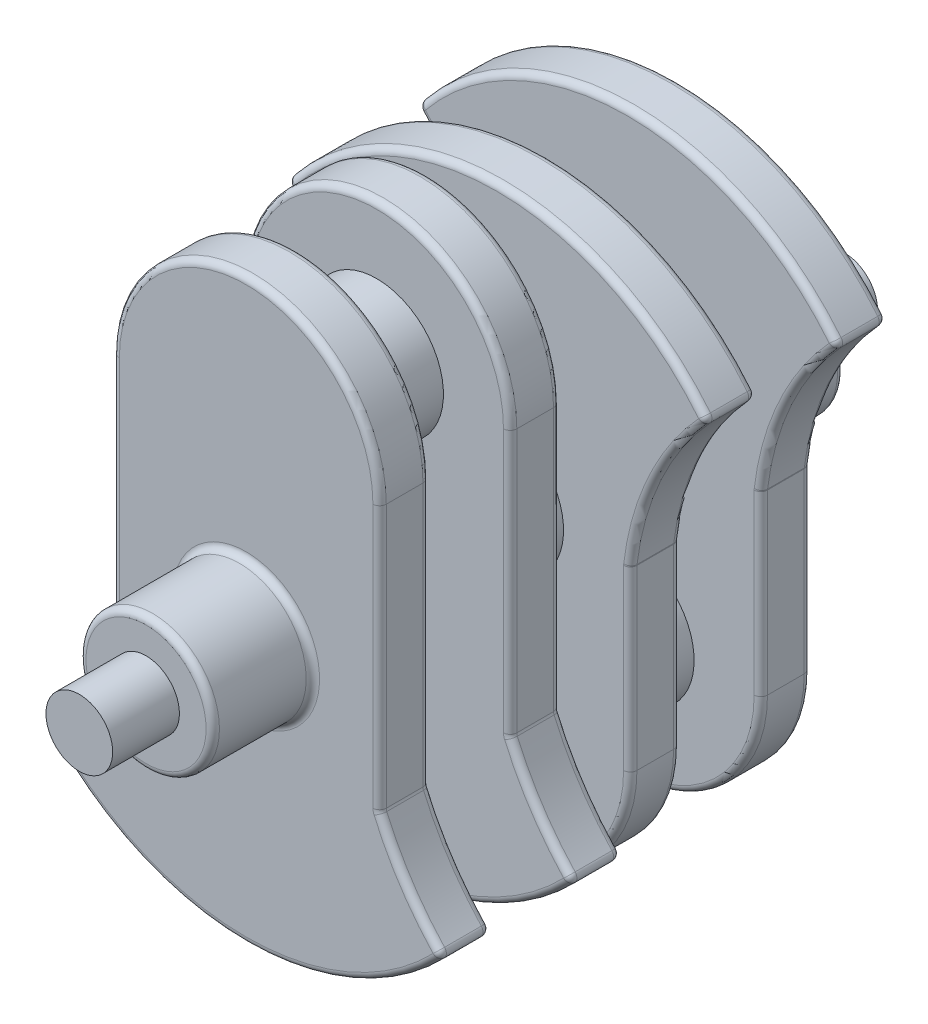
SolidWorks part; units mm, degrees
material "AISI 4340 Steel, normalized"
ref_plane "Front Plane" through (0, 0, 0) normal (0, 0, 1) x (1, 0, 0)
ref_plane "Top Plane" through (0, 0, 0) normal (0, 1, 0) x (1, 0, 0)
ref_plane "Right Plane" through (0, 0, 0) normal (1, 0, 0) x (0, 0, -1)
sketch "Sketch1" plane through (0, 0, 0) normal (0, 0, 1) x (1, 0, 0)
  circle A0 centre (0, 0) radius 20
  dimension "D1" = 20
extrude "Boss-Extrude1" add sketch "Sketch1" along normal blind 30
sketch "Sketch8" plane through (0, 0, 0) normal (0, 0, -1) x (-1, 0, 0)
  line L0 (-40, 53.333) -> (-40, -25.971)
  line L1 (40, 53.333) -> (40, -25.971)
  arc A0 (40, 53.333) -> (-40, 53.333) centre (0, 53.333) ccw
  arc A5 (-58.7669, -54.2813) -> (58.7669, -54.2813) centre (0, 0) ccw
  arc A6 (-40, -25.971) -> (-58.7669, -54.2813) centre (-125, 10) cw
  arc A7 (40, -25.971) -> (58.7669, -54.2813) centre (125, 10) ccw
  dimension "D1" = 40
  dimension "D2" = 80
  dimension "D3" = 53.333
  dimension "D5" = 10
  dimension "D6" = 125
extrude "Boss-Extrude5" add sketch "Sketch8" along normal blind 15
sketch "Sketch2" plane through (0, 0, 30) normal (0, 0, 1) x (1, 0, 0)
  circle A0 centre (0, 0) radius 10
  dimension "D1" = 10
extrude "Boss-Extrude2" add sketch "Sketch2" along normal blind 20
sketch "Sketch9" plane through (0, 0, -15) normal (0, 0, -1) x (-1, 0, 0)
  circle A0 centre (0, 53.333) radius 20
  dimension "D2" = 20
  dimension "D1" = 53.333
extrude "Boss-Extrude6" add sketch "Sketch9" along normal blind 24.13
ref_plane "Plane4" through (0, 0, -75.13) normal (0, 0, -1) x (-1, 0, 0)
sketch "Sketch10" plane through (0, 0, -39.13) normal (0, 0, -1) x (-1, 0, 0)
  line L0 (-40, -53.333) -> (-40, 0)
  line L1 (40, -53.333) -> (40, 0)
  arc A0 (-40, -53.333) -> (40, -53.333) centre (0, -53.333) ccw
  arc A1 (-40, 0) -> (-63.131, 49.1373) centre (-125, -10) ccw
  arc A2 (40, 0) -> (63.131, 49.1373) centre (125, -10) cw
  arc A3 (-63.131, 49.1373) -> (63.131, 49.1373) centre (0, 0) cw
  dimension "D1" = 40
  dimension "D5" = 10
  dimension "D3" = 80
  dimension "D2" = 53.333
  dimension "D4" = 125
extrude "Boss-Extrude7" add sketch "Sketch10" along normal blind 15 from surface starting at plane "Plane4"
ref_plane "Plane3" through (0, 0, -114.26) normal (0, 0, -1) x (-1, 0, 0)
sketch "Sketch12" plane through (0, 0, -114.26) normal (0, 0, -1) x (-1, 0, 0)
  line L2 (40, -53.333) -> (40, 0)
  line L3 (40, -53.333) -> (40, 0)
  line L4 (-40, 0) -> (-40, -53.333)
  line L5 (-40, 0) -> (-40, -53.333)
  arc A12 (-40, -53.333) -> (40, -53.333) centre (0, -53.333) ccw
  arc A13 (63.131, 49.1373) -> (40, 0) centre (125, -10) ccw
  arc A14 (63.131, 49.1373) -> (-63.131, 49.1373) centre (0, 0) ccw
  arc A15 (-40, 0) -> (-63.131, 49.1373) centre (-125, -10) ccw
  arc A16 (-40, -53.333) -> (40, -53.333) centre (0, -53.333) ccw
  arc A17 (63.131, 49.1373) -> (40, 0) centre (125, -10) ccw
  arc A18 (63.131, 49.1373) -> (-63.131, 49.1373) centre (0, 0) ccw
  arc A19 (-40, 0) -> (-63.131, 49.1373) centre (-125, -10) ccw
  dimension "D1" = 0
extrude "Boss-Extrude8" add sketch "Sketch12" along normal blind 15
sketch "Sketch14" plane through (0, 0, -90.13) normal (0, 0, -1) x (-1, 0, 0)
  circle A0 centre (0, -53.333) radius 20
  dimension "D2" = 20
  dimension "D1" = 53.333
extrude "Boss-Extrude9" add sketch "Sketch14" along normal up to next
sketch "Sketch15" plane through (0, 0, -129.26) normal (0, 0, -1) x (-1, 0, 0)
  circle A1 centre (0, 0) radius 20
  circle A2 centre (0, 0) radius 20
  dimension "D1" = 0
extrude "Boss-Extrude10" add sketch "Sketch15" along normal blind 30
sketch "Sketch16" plane through (0, 0, -159.26) normal (0, 0, -1) x (-1, 0, 0)
  circle A1 centre (0, 0) radius 10
  circle A2 centre (0, 0) radius 10
  dimension "D1" = 0
extrude "Boss-Extrude11" add sketch "Sketch16" along normal blind 20
sketch "Sketch18" plane through (0, 0, -39.13) normal (0, 0, -1) x (-1, 0, 0)
  line L2 (-40, 53.333) -> (-40, -25.971)
  line L3 (-40, 53.333) -> (-40, -25.971)
  line L4 (40, -25.971) -> (40, 53.333)
  line L5 (40, -25.971) -> (40, 53.333)
  arc A4 (40, 53.333) -> (-40, 53.333) centre (0, 53.333) ccw
  arc A5 (-58.7669, -54.2813) -> (-40, -25.971) centre (-125, 10) ccw
  arc A6 (-58.7669, -54.2813) -> (58.7669, -54.2813) centre (0, 0) ccw
  arc A7 (40, -25.971) -> (58.7669, -54.2813) centre (125, 10) ccw
  arc A8 (40, 53.333) -> (-40, 53.333) centre (0, 53.333) ccw
  arc A9 (-58.7669, -54.2813) -> (-40, -25.971) centre (-125, 10) ccw
  arc A10 (-58.7669, -54.2813) -> (58.7669, -54.2813) centre (0, 0) ccw
  arc A11 (40, -25.971) -> (58.7669, -54.2813) centre (125, 10) ccw
  dimension "D1" = 0
extrude "Boss-Extrude12" add sketch "Sketch18" along normal blind 15
sketch "Sketch19" plane through (0, 0, -54.13) normal (0, 0, -1) x (-1, 0, 0)
  circle A1 centre (0, 0) radius 20
  circle A2 centre (0, 0) radius 20
  dimension "D1" = 0
extrude "Boss-Extrude13" add sketch "Sketch19" along normal up to next
fillet "Fillet1" radius 2 32 edges at (0, -80, -39.13) (-48.0699, -40.9968, -39.13) (-40, 13.681, -39.13) (40, 13.681, -39.13) (48.0699, -40.9968, -39.13) (0, -80, -54.13) (-48.0699, -40.9968, -54.13) (-40, 13.681, -54.13) (0, 93.333, -54.13) (40, 13.681, -54.13) (48.0699, -40.9968, -54.13) (58.7669, -54.2813, -46.63) (40, -25.971, -46.63) (-40, -25.971, -46.63) (-58.7669, -54.2813, -46.63) (0, 93.333, -39.13) (40, 13.681, 0) (48.0699, -40.9968, 0) (0, -80, 0) (-48.0699, -40.9968, 0) (-40, 13.681, 0) (0, 93.333, -15) (40, 13.681, -15) (48.0699, -40.9968, -15) (0, -80, -15) (-48.0699, -40.9968, -15) (-40, 13.681, -15) (-40, -25.971, -7.5) (-58.7669, -54.2813, -7.5) (58.7669, -54.2813, -7.5) (40, -25.971, -7.5) (0, 93.333, 0)
fillet "Fillet2" radius 2 16 edges at (0, 80, -114.26) (47.5646, 26.4521, -114.26) (40, -26.6665, -114.26) (0, -93.333, -114.26) (-40, -26.6665, -114.26) (-47.5646, 26.4521, -114.26) (47.5646, 26.4521, -129.26) (40, -26.6665, -129.26) (0, -93.333, -129.26) (-40, -26.6665, -129.26) (-47.5646, 26.4521, -129.26) (-63.131, 49.1373, -121.76) (-40, 0, -121.76) (40, 0, -121.76) (63.131, 49.1373, -121.76) (0, 80, -129.26)
fillet "Fillet3" radius 2 16 edges at (40, -26.6665, -75.13) (47.5646, 26.4521, -75.13) (0, 80, -75.13) (-47.5646, 26.4521, -75.13) (-40, -26.6665, -75.13) (0, -93.333, -75.13) (40, -26.6665, -90.13) (47.5646, 26.4521, -90.13) (-47.5646, 26.4521, -90.13) (-40, -26.6665, -90.13) (0, -93.333, -90.13) (40, 0, -82.63) (63.131, 49.1373, -82.63) (-63.131, 49.1373, -82.63) (-40, 0, -82.63) (0, 80, -90.13)
fillet "Fillet5" radius 2 2 edges at (20, 0, 30) (20, 0, 0)
fillet "Fillet6" radius 2 2 edges at (-20, 0, -129.26) (-20, 0, -159.26)
ref_plane "Plane5" through (0, 31.75, 0) normal (0, 1, 0) x (1, 0, 0)
sketch "Sketch20" plane through (0, 0, 0) normal (1, 0, 0) x (0, 0, -1)
  line L1 (90.13, -73.333) -> (90.13, -33.333)
  line L2 (90.13, -73.333) -> (90.13, -33.333)
  dimension "D1" = 0
ref_plane "Plane6" through (0, -73.333, 0) normal (0, 1, 0) x (1, 0, 0)
sketch "Sketch21" plane through (0, 31.75, 0) normal (0, 1, 0) x (1, 0, 0)
  line L2 (-20, 157.26) -> (20, 157.26) construction
  line L3 (-20, 157.26) -> (-20, 131.26) construction
  line L4 (-20, 131.26) -> (20, 131.26) construction
  line L5 (20, 157.26) -> (20, 131.26) construction
  circle A0 centre (0, 144.26) radius 2.5
  point P10 (0, 157.26)
  point P11 (20, 144.26)
  dimension "D1" = 5
sketch "Sketch27" plane through (0, 0, 0) normal (0, 0, 1) x (1, 0, 0)
  line L0 (0, 73.333) -> (0, -20) construction
  circle A1 centre (0, 53.333) radius 20
  circle A2 centre (0, 53.333) radius 20 construction
  circle A3 centre (0, 0) radius 20
  circle A4 centre (0, 0) radius 20 construction
  dimension "D1" = 0
  dimension "D2" = 0
ref_plane "Plane8" through (0, 73.333, 0) normal (0, -1, 0) x (-1, 0, 0)
ref_plane "Plane9" through (0, -20, 0) normal (0, -1, 0) x (-1, 0, 0)
sketch "Sketch28" plane through (0, -20, 0) normal (0, -1, 0) x (-1, 0, 0)
  line L1 (-20, -2) -> (20, -2) construction
  line L2 (-20, -2) -> (-20, -28) construction
  line L3 (-20, -28) -> (20, -28) construction
  line L4 (20, -2) -> (20, -28) construction
  line L5 (-20, -2) -> (20, -28) construction
  line L6 (-20, -28) -> (20, -2) construction
  circle A0 centre (0, -15) radius 2.5
  point P4 (0, -15)
  dimension "D1" = 5
sketch "Sketch29" plane through (0, 73.333, 0) normal (0, -1, 0) x (-1, 0, 0)
  line L1 (20, 39.13) -> (-20, 39.13) construction
  line L2 (20, 39.13) -> (20, 15) construction
  line L3 (20, 15) -> (-20, 15) construction
  line L4 (-20, 39.13) -> (-20, 15) construction
  line L5 (20, 39.13) -> (-20, 15) construction
  line L6 (20, 15) -> (-20, 39.13) construction
  circle A0 centre (0, 27.065) radius 2.5
  point P4 (0, 27.065)
  dimension "D1" = 5
sketch "Sketch31" plane through (0, 0, 0) normal (1, 0, 0) x (0, 0, -1)
  line L0 (27.065, 73.333) -> (-15, -20) construction
ref_plane "Plane10" through (0, 73.333, -27.065) normal (0, -0.9117, 0.4109) x (-1, 0, 0)
hole_wizard "#4 (0.209) Diameter Hole2" positions "Sketch34" profile "Sketch35" hole size "#4" standard "ANSI Inch" end condition through all
sketch "Sketch34" plane through (0, 73.333, -27.065) normal (0, -0.9117, 0.4109) x (-1, 0, 0)
  point P0 (0, 0)
sketch "Sketch35" plane through (0, 73.333, -27.065) normal (1, 0, 0) x (0, 0.4109, 0.9117)
  line L0 (0, 0) -> (0, 171.4567)
  line L1 (0, 171.4567) -> (2.6543, 171.4567)
  line L2 (2.6543, 171.4567) -> (2.6543, 0.635)
  line L3 (2.6543, 0.635) -> (3.2893, 0)
  line L5 (3.2893, 0) -> (0, 0)
  line L6 (-2.6543, 0.635) -> (-3.2893, 0) construction
  line L11 (0, -6.35) -> (0, 107.95) construction
  dimension "Thru Hole Dia." = 5.3086
  dimension "Thru Hole Depth" = 171.4567
  dimension "Near C'Sink Dia." = 6.5786
  dimension "Near C'Sink Angle" = 90
ref_plane "Plane11" through (0, -20, 15) normal (0, -0.9117, 0.4109) x (-1, 0, 0)
hole_wizard "#4 (0.209) Diameter Hole3" positions "Sketch37" profile "Sketch38" hole size "#4" standard "ANSI Inch" end condition through all
sketch "Sketch37" plane through (0, -20, 15) normal (0, -0.9117, 0.4109) x (-1, 0, 0)
  point P0 (0, 0)
sketch "Sketch38" plane through (0, -20, 15) normal (1, 0, 0) x (0, -0.4109, -0.9117)
  line L0 (0, 0) -> (0, 170.9886)
  line L1 (0, 170.9886) -> (2.6543, 170.9886)
  line L2 (2.6543, 170.9886) -> (2.6543, 0.635)
  line L3 (2.6543, 0.635) -> (3.2893, 0)
  line L5 (3.2893, 0) -> (0, 0)
  line L6 (-2.6543, 0.635) -> (-3.2893, 0) construction
  line L11 (0, -6.35) -> (0, 107.95) construction
  dimension "Thru Hole Dia." = 5.3086
  dimension "Thru Hole Depth" = 170.9886
  dimension "Near C'Sink Dia." = 6.5786
  dimension "Near C'Sink Angle" = 90
combine bodies "Combine1" operation type add bodies to combine 123 109 117
equation "\"Crank Radius\" = 53.333mm"
equation "\"D1@Sketch9\"=\"Crank Radius\""
equation "\"D1@Sketch14\"=\"Crank Radius\""
equation "\"Journal Radius\" = 20mm"
equation "\"D1@Sketch1\"=\"Journal Radius\""
equation "\"D2@Sketch9\"=\"Journal Radius\""
equation "\"D2@Sketch14\"=\"Journal Radius\""
equation "\"Lobe Thickness\" = 15mm"
equation "\"D1@Boss-Extrude5\"=\"Lobe Thickness\""
equation "\"D1@Boss-Extrude7\"=\"Lobe Thickness\""
equation "\"D1@Boss-Extrude8\"=\"Lobe Thickness\""
equation "\"D1@Boss-Extrude12\"=\"Lobe Thickness\""
equation "\"D3@Sketch8\"=\"Crank Radius\""
equation "\"D2@Sketch10\"=\"Crank Radius\""
